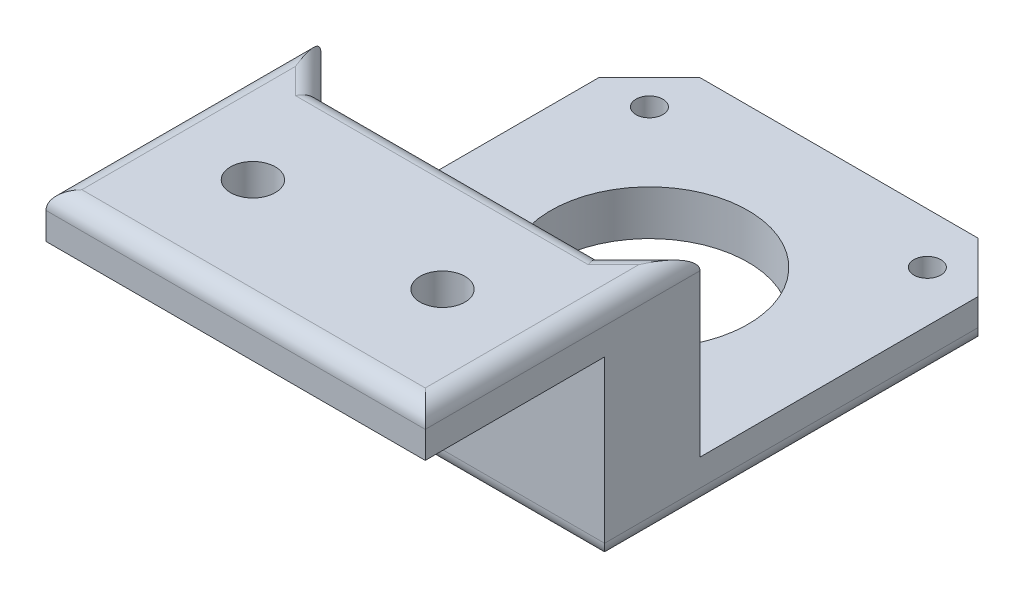
SolidWorks part; units mm, degrees
ref_plane "정면" through (0, 0, 0) normal (0, 0, 1) x (1, 0, 0)
ref_plane "윗면" through (0, 0, 0) normal (0, 1, 0) x (1, 0, 0)
ref_plane "우측면" through (0, 0, 0) normal (1, 0, 0) x (0, 0, -1)
sketch "스케치1" plane through (0, 0, 0) normal (1, 0, 0) x (0, 0, -1)
  line L1 (0, 0) -> (20, 0)
  line L2 (0, 0) -> (0, 5)
  line L3 (0, 5) -> (20, 5)
  line L4 (20, 0) -> (20, 5)
  line L5 (20, 5) -> (25, 5)
  line L6 (20, 5) -> (20, -20)
  line L7 (20, -20) -> (25, -20)
  line L8 (25, 5) -> (25, -20)
  line L9 (25, -20) -> (67.3, -20)
  line L10 (25, -20) -> (25, -15)
  line L11 (25, -15) -> (67.3, -15)
  line L12 (67.3, -20) -> (67.3, -15)
  dimension "D1" = 5
  dimension "D2" = 20
  dimension "D3" = 20
  dimension "D4" = 5
  dimension "D5" = 42.3
extrude "보스-돌출1" add sketch "스케치1" along normal blind 42.3 contours L9 L12 L11 L8 | L8 L5 L4 L6 L7 | L4 L1 L2 L3 region at (0, -7.5, -22.5) region at (0, -17.5, -46.15)
sketch "스케치2" plane through (0, 5, 0) normal (0, 1, 0) x (1, 0, 0)
  line L0 (0, 12.5) -> (42.3, 12.5) construction
  line L1 (0, 0) -> (0, 25) construction
  line L2 (42.3, 0) -> (42.3, 25) construction
  line L3 (21.15, 25) -> (21.15, 0) construction
  line L4 (42.3, 25) -> (0, 25) construction
  line L5 (42.3, 0) -> (0, 0) construction
  line L6 (10.575, 25) -> (10.575, 0) construction
  line L7 (31.725, 25) -> (31.725, 0) construction
  line L8 (0, 46.15) -> (42.3, 46.15) construction
  line L9 (21.15, 67.3) -> (21.15, 25) construction
  line L10 (42.3, 67.3) -> (0, 67.3) construction
  line L11 (0, 25) -> (0, 67.3) construction
  line L12 (42.3, 25) -> (42.3, 67.3) construction
  line L13 (5.65, 67.3) -> (0, 61.65)
  line L14 (5.65, 30.65) -> (36.65, 30.65)
  line L15 (5.65, 30.65) -> (5.65, 61.65)
  line L16 (5.65, 61.65) -> (36.65, 61.65)
  line L17 (36.65, 30.65) -> (36.65, 61.65)
  line L18 (5.65, 30.65) -> (36.65, 61.65) construction
  line L19 (5.65, 61.65) -> (36.65, 30.65) construction
  line L20 (36.65, 67.3) -> (42.3, 61.65)
  line L21 (36.65, 25) -> (42.3, 30.65)
  line L22 (5.65, 25) -> (0, 30.65)
  line L23 (0, 67.3) -> (0, 25)
  line L24 (0, 25) -> (42.3, 25)
  line L25 (42.3, 25) -> (42.3, 67.3)
  line L26 (42.3, 67.3) -> (0, 67.3)
  line L27 (0, 61.65) -> (0, 35)
  line L28 (10, 25) -> (32.3, 25)
  line L29 (42.3, 35) -> (42.3, 57.3)
  line L30 (32.3, 67.3) -> (5.65, 67.3)
  line L44 (0, 25) -> (42.3, 25)
  line L45 (0, 25) -> (0, 67.3)
  line L46 (0, 67.3) -> (42.3, 67.3)
  line L47 (42.3, 25) -> (42.3, 67.3)
  circle A0 centre (10.575, 12.5) radius 2.5
  circle A1 centre (31.725, 12.5) radius 2.5
  circle A2 centre (5.65, 61.65) radius 1.5
  circle A3 centre (5.65, 30.65) radius 1.5
  circle A4 centre (36.65, 30.65) radius 1.5
  circle A5 centre (36.65, 61.65) radius 1.5
  circle A6 centre (21.15, 46.15) radius 11
  point P29 (21.15, 46.15)
  line M4 (42.3, 25) -> (0, 25)
  dimension "D2" = 5
  dimension "D4" = 3
  dimension "D6" = 22
  dimension "D1" = 10.575
  dimension "D3" = 31
  dimension "D5" = 0
extrude "컷-돌출1" cut sketch "스케치2" against normal through all contours L46 L45 L13 | L20 L47 L46 | A6 | A2 | A5 | A3 | A4 | A0 | A1 region at (1.8833, 5, -65.4167) region at (40.4167, 5, -65.4167) region at (21.15, 5, -46.15)
extrude "보스-돌출2" add sketch "스케치2<4>" against normal up to vertex (20 mm away) contours L45 L22 M4 | L47 L21 M4 region at (1.8833, 5, -26.8833) region at (40.4167, 5, -26.8833) up to point (0, -15, -61.65)
sketch "스케치2<4>" plane through (0, 5, 0) normal (0, 1, 0) x (1, 0, 0) same geometry as "스케치2"
fillet "필렛1" radius 2 10 edges at (21.15, -20, -67.3) (42.3, -20, -40.825) (0, -20, -40.825) (21.15, -20, -20) (2.825, 5, -27.825) (21.15, 5, -25) (39.475, 5, -27.825) (21.15, 5, 0) (0, 5, -15.325) (42.3, 5, -15.325)
